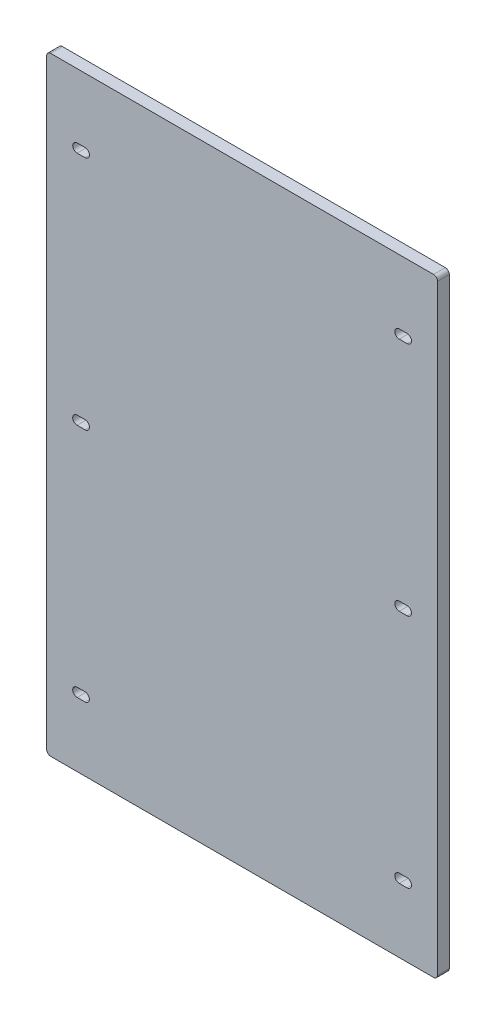
SolidWorks part; units mm, degrees
ref_plane "Alzado" through (0, 0, 0) normal (0, 0, 1) x (1, 0, 0)
ref_plane "Planta" through (0, 0, 0) normal (0, 1, 0) x (1, 0, 0)
ref_plane "Vista lateral" through (0, 0, 0) normal (1, 0, 0) x (0, 0, -1)
sketch "Croquis1" plane through (0, 0, 0) normal (0, 0, 1) x (1, 0, 0)
  line L1 (99.5, -155) -> (-99.5, -155)
  line L2 (99.5, -155) -> (99.5, 155)
  line L3 (99.5, 155) -> (-99.5, 155)
  line L4 (-99.5, -155) -> (-99.5, 155)
  line L5 (99.5, -155) -> (-99.5, 155) construction
  line L6 (99.5, 155) -> (-99.5, -155) construction
  point P0 (0, 0)
  dimension "D1" = 310
  dimension "D2" = 199
sheet metal parameters "Chapa metálica1" thickness 6 parameters "D1"=0.7366, "Espesor"=6
base flange "Brida base1" sketch "Croquis1" thickness 6 reverse thickness direction no parameters "D1"=0.7366
sketch "Croquis4" plane through (0, 0, 0) normal (0, 0, 1) x (1, 0, 0)
  line L0 (-84, 0) -> (-80, 0) construction
  line L1 (-84, 2.25) -> (-80, 2.25)
  line L2 (-84, -2.25) -> (-80, -2.25)
  line L3 (-82, 0) -> (0, 0) construction
  arc A0 (-84, 2.25) -> (-84, -2.25) centre (-84, 0) ccw
  arc A1 (-80, -2.25) -> (-80, 2.25) centre (-80, 0) ccw
  point P2 (-82, 0)
  dimension "D1" = 4.5
  dimension "D2" = 4
  dimension "D3" = 82
extrude "Cortar-Extruir1" cut sketch "Croquis4" against normal blind 10 normal cut yes
pattern_linear "MatrizL1" count 2 spacing 120 along (0, 1, 0) count 2 spacing 120 along (0, -1, 0) of "Cortar-Extruir1"
mirror "Simetría1" about plane through (0, 0, 0) normal (1, 0, 0) of "MatrizL1"
fillet "Redondeo1" radius 2 4 edges at (-99.5, -155, -3) (99.5, -155, -3) (99.5, 155, -3) (-99.5, 155, -3)
flat pattern "Chapa desplegada1" [suppressed]
sketch "Líneas de pliegue1" plane through (0, 0, 0) normal (0, 1, 0) x (1, 0, 0)
sketch "Cuadro delimitador1" [suppressed] plane through (0, 0, 0) normal (0, 1, 0) x (1, 0, 0)
